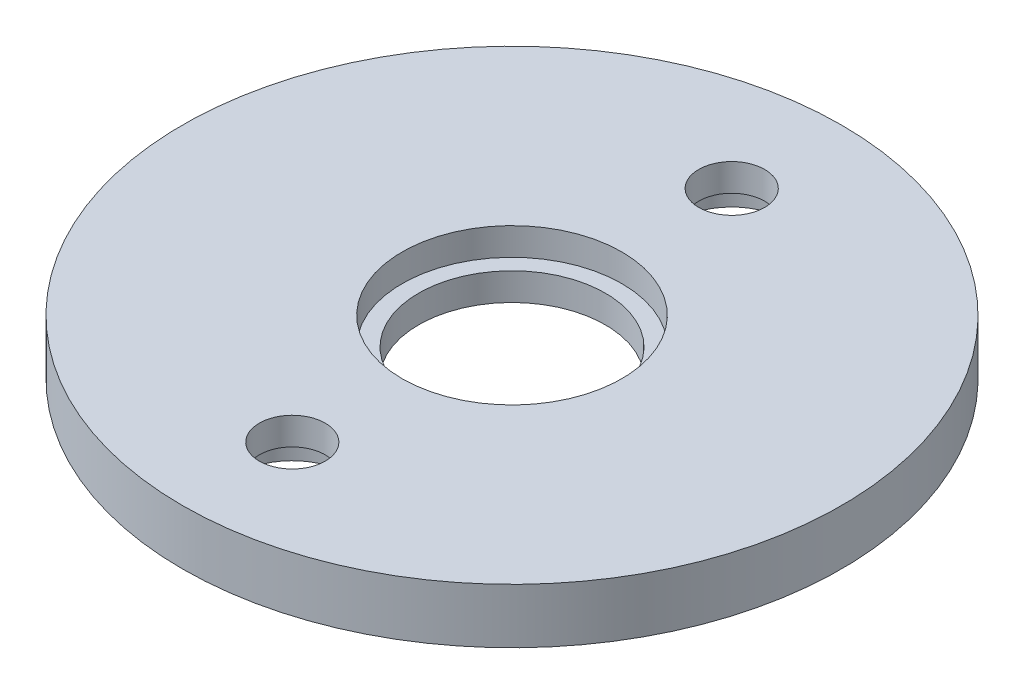
SolidWorks part; units mm, degrees
ref_plane "Front Plane" through (0, 0, 0) normal (0, 0, 1) x (1, 0, 0)
ref_plane "Top Plane" through (0, 0, 0) normal (0, 1, 0) x (1, 0, 0)
ref_plane "Right Plane" through (0, 0, 0) normal (1, 0, 0) x (0, 0, -1)
sketch "Sketch1" plane through (0, 0, 0) normal (0, 1, 0) x (1, 0, 0)
  line L0 (0, 0) -> (0, 4) construction
  line L1 (0, 0) -> (-2.2751, 0) construction
  circle A0 centre (0, 0) radius 6
  circle A1 centre (0, 4) radius 0.6
  circle A2 centre (0, 4) radius 1
  circle A3 centre (0, -4) radius 1
  circle A4 centre (0, -4) radius 0.6
  circle A5 centre (0, 0) radius 1.7
  dimension "D1" = 12
  dimension "D3" = 1.2
  dimension "D4" = 2
  dimension "D5" = 3.4
  dimension "D2" = 4
extrude "BasePlate" add sketch "Sketch1" along normal blind 1 contours A0 A5 A2 A3 | A4 | A1 | A2 A1 | A3 A4 region at (-5.8303, 0, 0) region at (0, 0, -4) region at (-0.9717, 0, -4) region at (-0.9717, 0, 4) region at (0, 0, 4)
extrude "ScrewHoles" cut sketch "Sketch1<3>" along normal through all contours A4 | A1 region at (0, 0, -4) region at (0, 0, 4)
sketch "Sketch1<3>" plane through (0, 0, 0) normal (0, 1, 0) x (1, 0, 0) same geometry as "Sketch1"
extrude "ScrewHatSlots" cut sketch "Sketch1<4>" along normal blind 0.5 contours A3 A4 | A2 A1 region at (-0.9717, 0, -4) region at (-0.9717, 0, 4)
sketch "Sketch1<4>" plane through (0, 0, 0) normal (0, 1, 0) x (1, 0, 0) same geometry as "Sketch1"
sketch "Sketch2" plane through (0, 1, 0) normal (0, 1, 0) x (1, 0, 0)
  circle A0 centre (0, 0) radius 2
  dimension "D1" = 4
extrude "BearingSlot" cut sketch "Sketch2" against normal offset from surface (0.5 mm away) 0.5 up to face at (0, 0, 1.7)
equation "\"BoltD\"=2mm"
equation "\"BoltHatD\"=3.2mm"
equation "\"NutShortSide\"=4mm"
equation "\"NutLongSide\"=4.5mm"
equation "\"SmallScrewD\"=1.2mm"
equation "\"SmallScrewHatD\"=2mm"
equation "\"TubeOuterD\"=1.2mm"
equation "\"BasicPulleyD\"=15mm"
equation "\"GrooveDepth\"=0.7mm"
equation "\"Cable1D\"=0.4mm"
equation "\"Cable2D\"=0.3mm"
equation "\"BallBearingInnerD\"=2mm"
equation "\"BallBearingOuterD\"=4mm"
equation "\"BallBearingThickness\"=2mm"
equation "\"BearingCapD\"=12mm"
equation "\"HumerusL\"=37.2mm"
equation "\"HumerusElbowSidePulleyD\"=10mm"
equation "\"RadiusL\"=68.1mm"
equation "\"Finger1L\"=120mm"
equation "\"Finger2L\"=100mm"
equation "\"Finger3L\"=80mm"
equation "\"ElbowExtendedAngle\"=140deg"
equation "\"D1@Sketch1\"=\"BearingCapD\""
equation "\"D3@Sketch1\"=\"SmallScrewD\""
equation "\"D4@Sketch1\"=\"SmallScrewHatD\""
equation "\"D5@Sketch1\"=\"BallBearingOuterD\"-0.6"
equation "\"D1@Sketch2\"=\"BallBearingOuterD\""
equation "\"TubeClipW\"=1.5mm"
equation "\"TubeClipH\"=1mm"
equation "\"TubeClipLock_SideL\"=1.6mm"
equation "\"TubeClipLock_W\"=0.7mm"
equation "\"ElbowFlexedAngle\"=38deg"
equation "\"Digit5ExtendedAngle\"=80deg"
equation "\"Digit5FlexedAngle\"=24deg"
equation "\"Digit4ExtendedAngle\"=108deg"
equation "\"Digit4FlexedAngle\"=34deg"
equation "\"Digit3ExtendedAngle\"=145deg"
equation "\"Digit3FlexedAngle\"=44deg"
equation "\"KST_ServoBoltShelfHeight\"=21.1mm"
equation "\"KST_ServoLength\"=23mm"
equation "\"KST_ServoWidth\"=12mm"
equation "\"KST_ServoBoltHole2HoleLength\"=28mm"
equation "\"KST_ServoBoltHole2ShaftDist\"=8.3mm"
equation "\"KST_ServoBoltHole2HoleWidth\"=7mm"
equation "\"KST_ServoHeight\"=27.5mm"
equation "\"KST_ServoShaftHeight\"=3.5mm"
equation "\"KST_ServoShaftD\"=4.25mm"
equation "\"KST_ServoShaftToothL\"=0.345mm"
equation "\"KST_ServoToothAngle\"=60deg"
equation "\"KST_ServoToothTipWidth\"=0.18mm"
equation "\"KST_ServoToothFilletR\"=0.1mm"
equation "\"KST_ServoShaftToothN\"=25"
equation "\"KST_ServoBoltD\"=2mm"
equation "\"KST_ServoBoltHatD\"=5mm"
